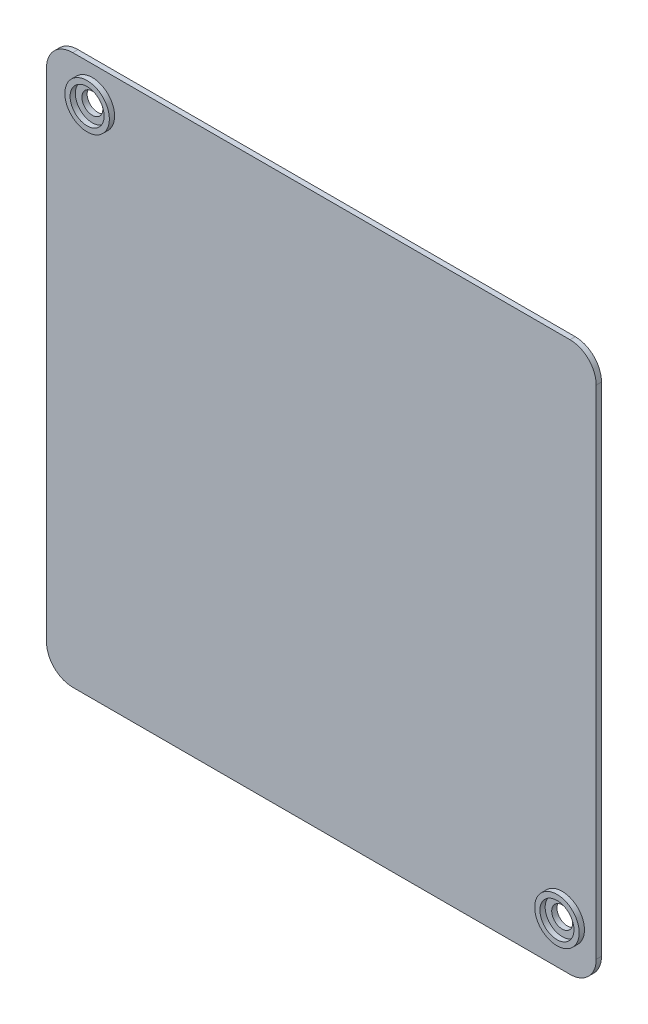
SolidWorks part; units mm, degrees
ref_plane "Plan de face" through (0, 0, 0) normal (0, 0, 1) x (1, 0, 0)
ref_plane "Plan de dessus" through (0, 0, 0) normal (0, 1, 0) x (1, 0, 0)
ref_plane "Plan de droite" through (0, 0, 0) normal (1, 0, 0) x (0, 0, -1)
sketch "Esquisse1" plane through (0, 0, 0) normal (0, 0, 1) x (1, 0, 0)
  line L0 (0, 0) -> (0, 52.5) construction
  line L1 (-52.5, 52.5) -> (52.5, 52.5)
  line L2 (-52.5, 52.5) -> (-52.5, -52.5)
  line L3 (-52.5, -52.5) -> (52.5, -52.5)
  line L4 (52.5, 52.5) -> (52.5, -52.5)
  line L5 (-52.5, -52.5) -> (52.5, 52.5) construction
  circle A0 centre (0, 0) radius 45 construction
  circle A1 centre (-43.75, 46) radius 3.25
  circle A2 centre (-43.75, 46) radius 4.25
  circle A3 centre (-43.75, 46) radius 2
  circle A4 centre (46, -43.75) radius 2
  circle A5 centre (46, -43.75) radius 3.25
  circle A6 centre (46, -43.75) radius 4.25
  point P11 (0, 45)
  dimension "D1" = 90
  dimension "D6" = 6.5
  dimension "D7" = 1
  dimension "D8" = 4
  dimension "D2" = 52.5
  dimension "D3" = 105
  dimension "D4" = 105
  dimension "D5" = 52.5
  dimension "D9" = 43.75
  dimension "D10" = 1
extrude "Boss.-Extru.1" add sketch "Esquisse1" along normal blind 1 contours L4 L1 L2 L3 A2 A6 | A2 A1 | A1 A3 | A6 A5 | A5 A4 region at (-0.0117, -0.0117, 0) region at (-46.9081, 46, 0) region at (-47.8798, 46, 0) region at (42.8419, -43.75, 0) region at (41.8702, -43.75, 0)
extrude "Boss.-Extru.3" add sketch "Esquisse1<4>" along normal blind 2 contours A2 A1 | A6 A5 region at (-47.8798, 46, 0) region at (41.8702, -43.75, 0)
sketch "Esquisse1<4>" plane through (0, 0, 0) normal (0, 0, 1) x (1, 0, 0) same geometry as "Esquisse1"
fillet "Congé1" radius 5 4 edges at (52.5, -52.5, 0.5) (-52.5, -52.5, 0.5) (-52.5, 52.5, 0.5) (52.5, 52.5, 0.5)
